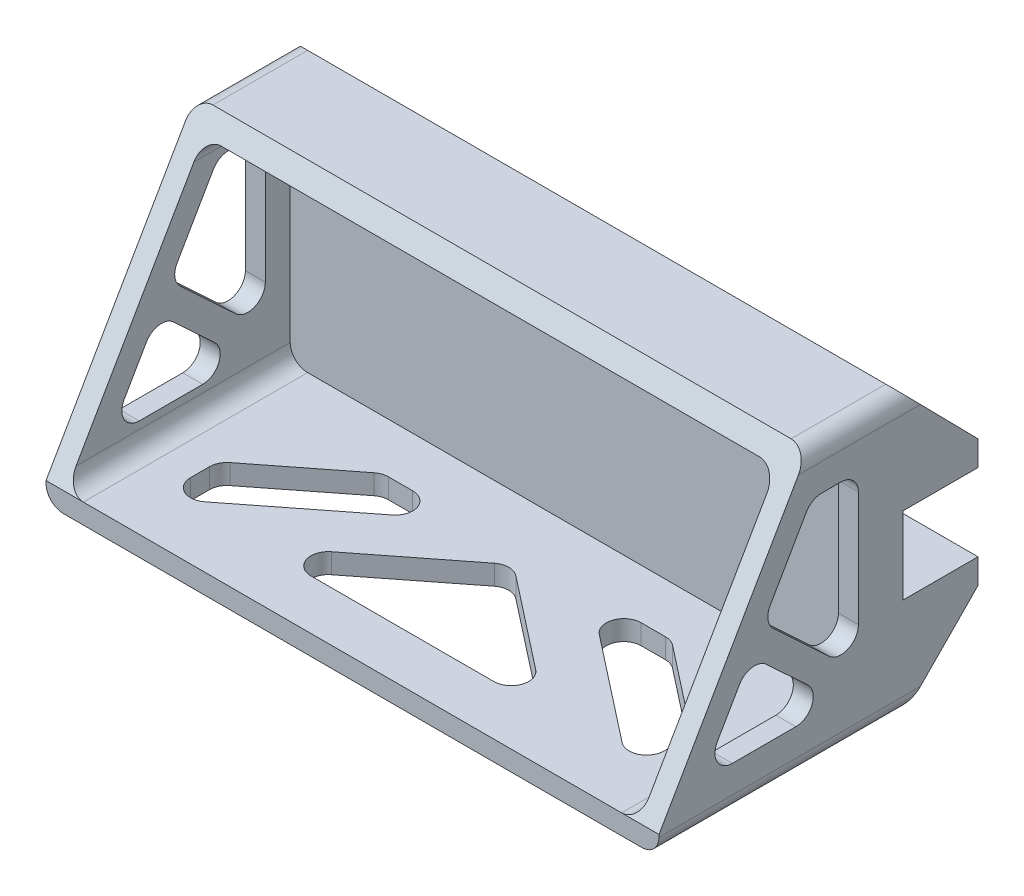
SolidWorks part; units mm, degrees
ref_plane "Front Plane" through (0, 0, 0) normal (0, 0, 1) x (1, 0, 0)
ref_plane "Top Plane" through (0, 0, 0) normal (0, 1, 0) x (1, 0, 0)
ref_plane "Right Plane" through (0, 0, 0) normal (1, 0, 0) x (0, 0, -1)
sketch "Sketch1" plane through (0, 0, 0) normal (0, 0, 1) x (1, 0, 0)
  line L0 (-61.5, 28) -> (61.5, 28)
  line L1 (-57.5, -24) -> (57.5, -24)
  line L2 (-57.5, -24) -> (-57.5, 24)
  line L3 (-57.5, 24) -> (57.5, 24)
  line L4 (57.5, -24) -> (57.5, 24)
  line L5 (-57.5, -24) -> (57.5, 24) construction
  line L6 (-57.5, 24) -> (57.5, -24) construction
  line L7 (61.5, -28) -> (61.5, 28)
  line L8 (-61.5, -28) -> (61.5, -28)
  line L9 (-61.5, -28) -> (-61.5, 28)
  point P0 (0, 0)
  dimension "D1" = 48
  dimension "D2" = 115
  dimension "D3" = 4
extrude "Boss-Extrude1" add sketch "Sketch1" along normal blind 4 contours L1 L4 L3 L2 | L9 L8 L7 L0 L4 L1 L2 L3 region at (0, 26.6485, 0) region at (0, 0, 0)
extrude "Boss-Extrude2" add sketch "Sketch1<3>" along normal blind 49
sketch "Sketch1<3>" plane through (0, 0, 0) normal (0, 0, 1) x (1, 0, 0) same geometry as "Sketch1"
sketch "Sketch2" plane through (0, 0, 0) normal (0, 0, -1) x (-1, 0, 0)
  line L1 (61.5, 7.75) -> (-61.5, 7.75)
  line L2 (61.5, 7.75) -> (61.5, -7.75)
  line L3 (61.5, -7.75) -> (-61.5, -7.75)
  line L4 (-61.5, 7.75) -> (-61.5, -7.75)
  line L5 (61.5, 7.75) -> (-61.5, -7.75) construction
  line L6 (61.5, -7.75) -> (-61.5, 7.75) construction
  line L7 (-61.5, -28) -> (-61.5, 28) construction
  line L8 (61.5, -28) -> (61.5, 28) construction
  line L9 (-61.5, -7.75) -> (61.5, -7.75)
  line L10 (-61.5, -7.75) -> (-61.5, -12.75)
  line L11 (-61.5, -12.75) -> (61.5, -12.75)
  line L12 (61.5, -7.75) -> (61.5, -12.75)
  line L14 (-61.5, 7.75) -> (61.5, 7.75)
  line L15 (-61.5, 7.75) -> (-61.5, 12.75)
  line L16 (-61.5, 12.75) -> (61.5, 12.75)
  line L17 (61.5, 7.75) -> (61.5, 12.75)
  point P0 (0, 0)
  line M1 (61.5, -28) -> (61.5, 28)
  line M3 (-61.5, 28) -> (-61.5, -28)
  dimension "D1" = 15.5
  dimension "D2" = 123
  dimension "D3" = 5
  dimension "D4" = 5
extrude "Boss-Extrude3" add sketch "Sketch2" along normal blind 15 contours L11 L3 M3 M1 | L16 L1 M3 M1 region at (0, 10.25, 0) region at (0, -10.25, 0)
sketch "Sketch3" plane through (61.5, 0, 0) normal (1, 0, 0) x (0, 0, -1)
  line L0 (0, -28) -> (15, -12.75)
  line L1 (15, -12.75) -> (0, -12.75)
  line L2 (0, -12.75) -> (0, -28)
  line L3 (15, 12.75) -> (0, 28)
  line L4 (0, 28) -> (0, 12.75)
  line L5 (0, 12.75) -> (15, 12.75)
extrude "Boss-Extrude4" add sketch "Sketch3" against normal blind 5
ref_plane "Plane1" through (0, 0, 0) normal (-1, 0, 0) x (0, 0, 1)
mirror "Mirror1" about plane through (0, 0, 0) normal (-1, 0, 0) of "Boss-Extrude4"
sketch "Sketch4" plane through (-61.5, 0, 0) normal (-1, 0, 0) x (0, 0, 1)
  line L0 (49, -24) -> (49, 24) construction
  line L1 (4, 24) -> (4, -24) construction
  line L2 (49, -24) -> (49, 24)
  line L3 (4, 24) -> (4, -24)
  line L4 (49, -24) -> (19, 28)
  line L5 (49, 28) -> (0, 28) construction
  line L6 (4, 24) -> (4, 28)
  line L7 (49, -28) -> (4, -28)
  line L8 (49, -28) -> (0, -28) construction
  line L9 (4, -28) -> (4, -24)
  line L10 (49, -24) -> (49, -28)
  line L11 (19, 28) -> (49, 28)
  line L12 (49, 28) -> (49, 24)
  line M3 (49, 28) -> (0, 28)
  line M12 (49, -28) -> (49, 28)
  dimension "D1" = 15
extrude "Cut-Extrude1" cut sketch "Sketch4" against normal through all contours L4 M12 M3 region at (-61.5, 10.6667, 39)
sketch "Sketch6" plane through (-61.5, 0, 0) normal (-1, 0, 0) x (0, 0, 1)
  line L0 (40.3429, -19) -> (30.6636, -2.2225)
  line L1 (18.4199, 19) -> (9, 19)
  line L2 (9, 19) -> (9, -15.5822)
  line L3 (12.6663, -19) -> (40.3429, -19)
  line L4 (4, -24) -> (49, -24)
  line L5 (49, -24) -> (21.3077, 24)
  line L6 (21.3077, 24) -> (4, 24)
  line L7 (4, 24) -> (4, -24)
  line L8 (4, -24) -> (49, -24)
  line L9 (49, -24) -> (21.3077, 24)
  line L10 (21.3077, 24) -> (4, 24)
  line L11 (4, 24) -> (4, -24)
  line L13 (12.6663, -19) -> (30.6636, -2.2225)
  line L14 (9, -15.5822) -> (27.6767, 1.8287)
  line L15 (27.6767, 1.8287) -> (28.0887, 2.2407)
  line L17 (28.0887, 2.2407) -> (18.4199, 19)
  line L18 (40.3429, -19) -> (18.4199, 19) construction
  line L20 (9, -19) -> (40.3429, -19) construction
  line L21 (9, 19) -> (9, -19) construction
  dimension "D1" = 0
  dimension "D2" = 5
extrude "Cut-Extrude2" cut sketch "Sketch6" against normal through all contours L13 L3 L0 | L17 L1 L2 L14 L15 region at (-61.5, -13.4075, 27.891)
sketch "Sketch7" plane through (0, -28, 0) normal (0, -1, 0) x (1, 0, 0)
  line L0 (-47.5, 41.1739) -> (-12.7778, 14)
  line L1 (12.7778, 14) -> (47.5, 41.1739)
  line L3 (0, 16.6983) -> (51.3369, 56.8751) construction
  line L4 (57.5, 4) -> (57.5, 49)
  line L5 (-57.5, 4) -> (57.5, 4)
  line L6 (-57.5, 49) -> (-57.5, 4)
  line L7 (57.5, 49) -> (-57.5, 49)
  line L11 (47.5, 49) -> (-57.5, 49)
  line L12 (0, 16.6983) -> (28.4966, 39)
  line L13 (-47.5, 28.4756) -> (-29.0034, 14)
  line L14 (-28.4966, 39) -> (0, 16.6983)
  line L15 (-51.3369, 56.8751) -> (0, 16.6983) construction
  line L16 (28.4966, 39) -> (-28.4966, 39)
  line L17 (47.5, 28.4756) -> (47.5, 41.1739)
  line L18 (-47.5, 41.1739) -> (-47.5, 28.4756)
  line L19 (-29.0034, 14) -> (-12.7778, 14)
  line L21 (-57.5, 49) -> (0, 4) construction
  line L23 (-63.6631, 41.1249) -> (0, -8.6983) construction
  line L26 (12.7778, 14) -> (29.0034, 14)
  line L28 (0, 4) -> (57.5, 49) construction
  line L29 (29.0034, 14) -> (47.5, 28.4756)
  line L30 (0, -8.6983) -> (63.6631, 41.1249) construction
  dimension "D2" = 10
  dimension "D1" = 0
extrude "Cut-Extrude3" cut sketch "Sketch7" against normal blind 5 contours L12 L16 L14 | L13 L19 L0 L18 | L26 L29 L17 L1 region at (-33.7831, -28, 24.735) region at (33.7831, -28, 24.735) region at (0, -28, 31.5661)
fillet "Fillet5" radius 3.5 11 edges at (-12.7778, -26, 14) (12.7778, -26, 14) (47.5, -26, 41.1739) (28.4966, -26, 39) (-47.5, -26, 41.1739) (-47.5, -26, 28.4756) (-28.4966, -26, 39) (47.5, -26, 28.4756) (29.0034, -26, 14) (0, -26, 16.6983) (-29.0034, -26, 14)
fillet "Fillet6" radius 3.5 14 edges at (-59.5, 19, 18.4199) (-59.5, 19, 9) (-59.5, -15.5822, 9) (-59.5, -19, 12.6663) (-59.5, -19, 40.3429) (-59.5, -2.2225, 30.6636) (-59.5, 2.2407, 28.0887) (59.5, -2.2225, 30.6636) (59.5, 2.2407, 28.0887) (59.5, -19, 40.3429) (59.5, 19, 9) (59.5, 19, 18.4199) (59.5, -19, 12.6663) (59.5, -15.5822, 9)
fillet "Fillet7" radius 3.5 4 edges at (-57.5, 24, 12.6538) (-57.5, -24, 26.5) (57.5, 24, 12.6538) (57.5, -24, 26.5)
fillet "Fillet8" radius 3.5 4 edges at (-61.5, -28, 24.5) (61.5, -28, 24.5) (61.5, 28, 9.5) (-61.5, 28, 9.5)
sketch "Sketch8" plane through (0, 12.75, 0) normal (0, 1, 0) x (1, 0, 0)
  line L0 (0, 0) -> (0, 15) construction
  line L1 (56.5, 0) -> (-56.5, 0) construction
  line L2 (56.5, 15) -> (-56.5, 15) construction
  circle A0 centre (40, 7.5) radius 1.75
  circle A1 centre (-40, 7.5) radius 1.75
  dimension "D1" = 3.5
  dimension "D2" = 40
extrude "Cut-Extrude4" cut sketch "Sketch8" against normal through all
